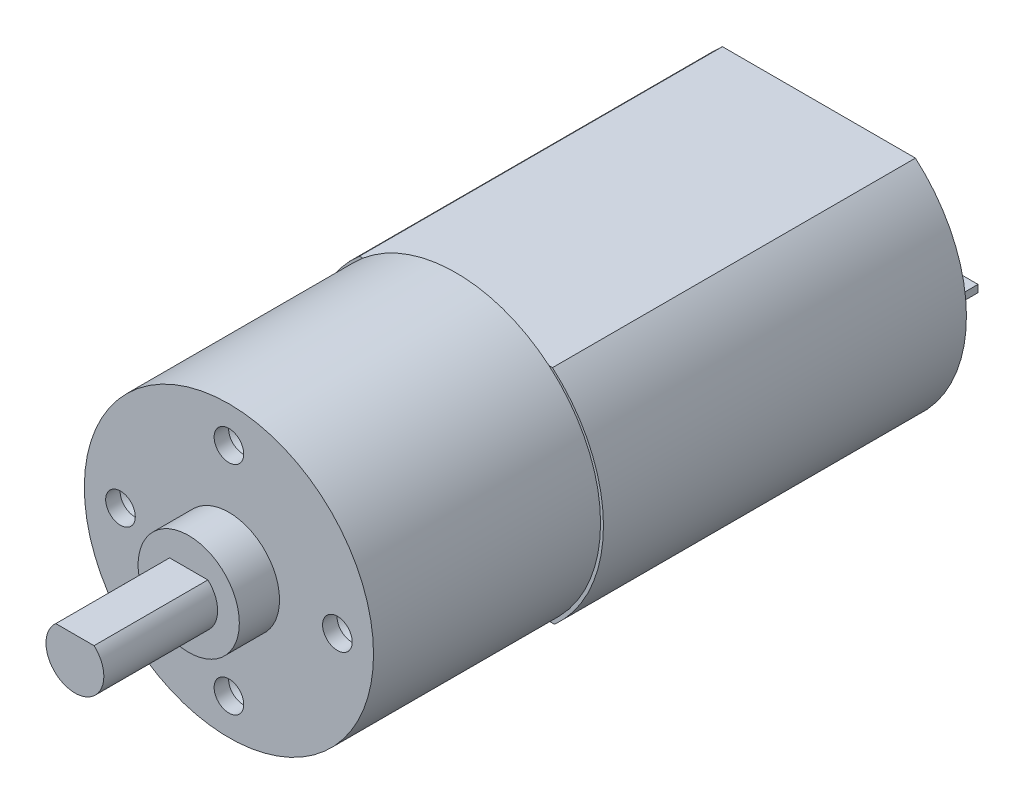
SolidWorks part; units mm, degrees
material "ASTM A36 Steel"
ref_plane "Front Plane" through (0, 0, 0) normal (0, 0, 1) x (1, 0, 0)
ref_plane "Top Plane" through (0, 0, 0) normal (0, 1, 0) x (1, 0, 0)
ref_plane "Right Plane" through (0, 0, 0) normal (1, 0, 0) x (0, 0, -1)
sketch "Sketch1" plane through (0, 0, 0) normal (0, 0, 1) x (1, 0, 0)
  circle A0 centre (0, 0) radius 10
  dimension "D1" = 20
extrude "GearBox" add sketch "Sketch1" along normal blind 15.7
sketch "Sketch3" plane through (0, 0, 0) normal (0, 0, -1) x (-1, 0, 0)
  line L0 (0, 4.9186) -> (0, -5.0461) construction
  line L3 (-6.0008, 0) -> (6.0008, 0) construction
  line L6 (-6.6744, 7.65) -> (6.6744, 7.65)
  line L7 (-6.819, -7.65) -> (6.819, -7.65)
  line L8 (8.635, 0) -> (-8.635, 0) construction
  line L9 (0, 8.635) -> (0, -8.635) construction
  arc A0 (-6.6744, 7.65) -> (-6.819, -7.65) centre (0, -0.0638) ccw
  arc A1 (6.819, -7.65) -> (6.6744, 7.65) centre (0, -0.0638) ccw
  point P8 (-10.2, 0.0326)
  point P9 (10.2, 0.0326)
  dimension "D1" = 15.3
  dimension "D3" = 20.4
  dimension "D2" = 7.65
extrude "Motor" add sketch "Sketch3" along normal blind 25.1
sketch "Sketch4" plane through (0, 0, 15.7) normal (0, 0, 1) x (1, 0, 0)
  line L0 (0, 4.9911) -> (0, -4.9911) construction
  line L3 (-6.0008, 0) -> (6.0007, 0) construction
  circle A0 centre (0, 0) radius 3.5
  dimension "D1" = 7
extrude "Output_Shaft_Collar" add sketch "Sketch4" along normal blind 2.78
sketch "Sketch5" plane through (0, 0, 18.48) normal (0, 0, 1) x (1, 0, 0)
  line L0 (0, 3.5) -> (0, -3.5) construction
  line L1 (-3.5, 0) -> (3.5, 0) construction
  line L2 (0, -7.454) -> (0, -2) construction
  line L3 (-2, 0) -> (2, 0) construction
  line L4 (-1.3229, 1.5) -> (1.3229, 1.5)
  circle A0 centre (0, 0) radius 3.5 construction
  arc A1 (-1.3229, 1.5) -> (1.3229, 1.5) centre (0, 0) ccw
  dimension "D1" = 4
  dimension "D2" = 3.5
extrude "Output_Shaft" add sketch "Sketch5" along normal blind 7.87
sketch "Sketch6" plane through (0, 0, -25.1) normal (0, 0, -1) x (-1, 0, 0)
  line L0 (0, 7.65) -> (0, -7.65) construction
  line L1 (6.6744, 7.65) -> (-6.6744, 7.65) construction
  line L2 (-6.819, -7.65) -> (6.819, -7.65) construction
  line L3 (10.2, -0.1601) -> (-10.2, -0.1601) construction
  arc A0 (-6.6744, 7.65) -> (-6.819, -7.65) centre (0, -0.0638) ccw construction
  arc A1 (6.819, -7.65) -> (6.6744, 7.65) centre (0, -0.0638) ccw construction
  circle A2 centre (0, 0) radius 3.02
  dimension "D1" = 6.04
extrude "Boss-Extrude11" add sketch "Sketch6" along normal blind 1.86
sketch "Sketch10" plane through (0, 0, -25.1) normal (0, 0, -1) x (-1, 0, 0)
  line L1 (11.2205, 0) -> (-11.2205, 0) construction
  line L2 (-6.64, -0.25) -> (-9, -0.25)
  line L3 (-6.64, -0.25) -> (-6.64, 0.25)
  line L4 (-6.64, 0.25) -> (-9, 0.25)
  line L5 (-9, -0.25) -> (-9, 0.25)
  line L6 (-6.64, -0.25) -> (-9, 0.25) construction
  line L7 (0, 5.1246) -> (0, -6.0856) construction
  line L8 (0, 11) -> (0, -11) construction
  line L9 (-6.64, 0.25) -> (-9, -0.25) construction
  line L10 (0, 10) -> (0, -10.5351) construction
  line L11 (6.64, 0.25) -> (9, -0.25) construction
  line L12 (6.64, -0.25) -> (9, 0.25) construction
  line L13 (9, -0.25) -> (9, 0.25)
  line L14 (6.64, 0.25) -> (9, 0.25)
  line L15 (6.64, -0.25) -> (6.64, 0.25)
  line L16 (6.64, -0.25) -> (9, -0.25)
  circle A0 centre (0, 0) radius 10 construction
  point P0 (-7.82, 0)
  point P20 (7.82, 0)
  dimension "D1" = 2.36
  dimension "D2" = 0.5
  dimension "D3" = 9
extrude "Boss-Extrude13" add sketch "Sketch10" along normal blind 2
hole_wizard "M2.5x0.45 Tapped Hole1" positions "Sketch12" profile "Sketch11" tap size "M2.5x0.45" standard "ANSI Metric"
sketch "Sketch12" plane through (0, 0, 15.7) normal (0, 0, 1) x (1, 0, 0)
  line L0 (11.2205, 0) -> (-11.2205, 0) construction
  line L2 (0, -11) -> (0, 11) construction
  point P0 (-7.5, 0)
  point P4 (7.5, 0)
  point P9 (0, 7.5)
  point P11 (0, -7.5)
  dimension "D1" = 15
  dimension "D2" = 7.5
  dimension "D3" = 15
  dimension "D4" = 7.5
sketch "Sketch11" plane through (-7.5, 0, 15.7) normal (1, 0, 0) x (0, -1, 0)
  line L0 (0, 0) -> (0, 1.6159)
  line L1 (0, 1.6159) -> (1.025, 1)
  line L2 (1.025, 1) -> (1.025, 0)
  line L5 (1.025, 0) -> (0, 0)
  line L10 (0, 1.6159) -> (-1.025, 1) construction
  line L11 (0, -6.35) -> (0, 107.95) construction
  dimension "Tap Drill Dia." = 2.05
  dimension "Tap Drill Depth" = 1
  dimension "Drill Angle" = 118
cosmetic thread "Hole Thread1" parameters "D1"=1, "D2"=2.5
cosmetic thread "Hole Thread2" parameters "D1"=1, "D2"=2.5
cosmetic thread "Hole Thread3" parameters "D1"=1, "D2"=2.5
cosmetic thread "Hole Thread4" parameters "D1"=1, "D2"=2.5
ref_axis "Axis1" through (0, 0, 31.0884) along (0, 0, -1)
